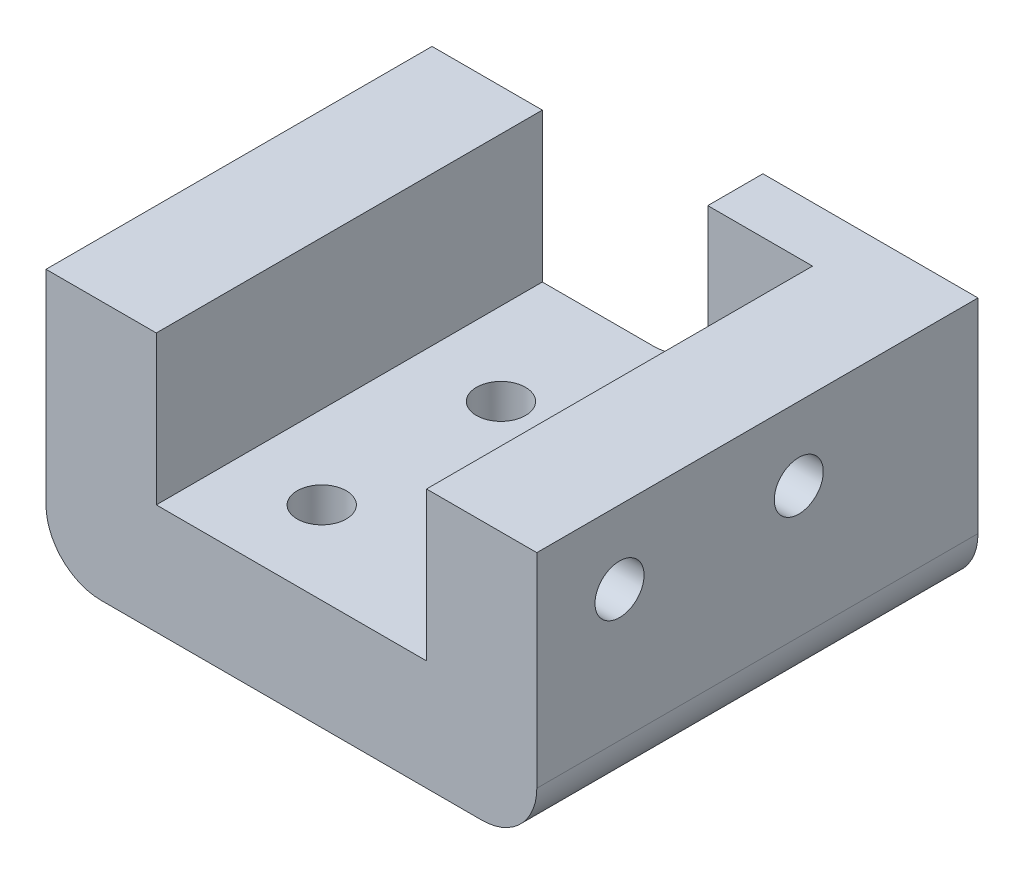
SolidWorks part; units mm, degrees
ref_plane "Front Plane" through (0, 0, 0) normal (0, 0, 1) x (1, 0, 0)
ref_plane "Top Plane" through (0, 0, 0) normal (0, 1, 0) x (1, 0, 0)
ref_plane "Right Plane" through (0, 0, 0) normal (1, 0, 0) x (0, 0, -1)
sketch "Sketch1" plane through (0, 0, 0) normal (0, 1, 0) x (1, 0, 0)
  line L0 (2.075, -3.5) -> (2.825, -3.5)
  line L1 (2.075, -3.5) -> (-2.075, -3.5)
  line L2 (2.075, -3.5) -> (2.075, 3.5) construction
  line L3 (2.075, 3.5) -> (-2.075, 3.5)
  line L4 (-2.075, -3.5) -> (-2.075, 3.5) construction
  line L5 (2.075, -3.5) -> (-2.075, 3.5) construction
  line L6 (2.075, 3.5) -> (-2.075, -3.5) construction
  line L7 (2.825, -3.5) -> (3.825, -3.5)
  line L9 (3.825, 3.5) -> (2.825, 3.5)
  line L10 (2.825, 3.5) -> (2.075, 3.5)
  line L11 (3.825, 3.5) -> (4.825, 3.5)
  line L12 (4.825, 3.5) -> (4.825, -3.5)
  line L13 (4.825, -3.5) -> (3.825, -3.5)
  line L14 (-2.075, 3.5) -> (-4.075, 3.5)
  line L15 (-4.075, 3.5) -> (-4.075, -3.5)
  line L16 (-4.075, -3.5) -> (-2.075, -3.5)
  line L17 (3.825, 3.5) -> (3.825, -3.5) construction
  point P0 (0, 0)
  dimension "D1" = 4.15
  dimension "D2" = 7
  dimension "D3" = 0.75
  dimension "D4" = 1
  dimension "D5" = 1
  dimension "D6" = 2
extrude "Boss-Extrude1" add sketch "Sketch1" along normal blind 2
sketch "Sketch2" plane through (0, 2, 0) normal (0, 1, 0) x (1, 0, 0)
  line L1 (-4.075, 3.5) -> (-2.075, 3.5)
  line L2 (-4.075, 3.5) -> (-4.075, -3.5)
  line L3 (-4.075, -3.5) -> (-2.075, -3.5)
  line L4 (-2.075, 3.5) -> (-2.075, -3.5)
  line L5 (2.825, 3.5) -> (4.825, 3.5)
  line L6 (2.825, 3.5) -> (2.825, -3.5)
  line L7 (2.825, -3.5) -> (4.825, -3.5)
  line L8 (4.825, 3.5) -> (4.825, -3.5)
extrude "Boss-Extrude2" add sketch "Sketch2" along normal blind 2.7
sketch "Sketch3" plane through (2.825, 0, 0) normal (-1, 0, 0) x (0, 0, 1)
  line L13 (-3.5, 4.7) -> (-3.5, 2) construction
  line L14 (-3.5, 2) -> (3.5, 2) construction
  line L15 (-3.5, 4.7) -> (-3.5, 0) construction
  circle A2 centre (-1.25, 3.375) radius 0.4445
  circle A3 centre (2, 3.375) radius 0.4445
  dimension "D4" = 0.889
  dimension "D1" = 1.375
  dimension "D2" = 2.25
  dimension "D3" = 5.5
extrude "Cut-Extrude1" cut sketch "Sketch3" against normal through all
sketch "Sketch5" plane through (0, 0, -3.5) normal (0, 0, -1) x (-1, 0, 0)
  line L0 (-2.075, 0) -> (2.075, 0) construction
  line L1 (-4.825, 4.7) -> (-0.925, 4.7)
  line L2 (-4.825, 4.7) -> (-4.825, 0)
  line L3 (-4.825, 0) -> (-0.925, 0)
  line L4 (-0.925, 4.7) -> (-0.925, 0)
  line L5 (2.075, 4.7) -> (2.075, 2) construction
  dimension "D1" = 3
extrude "Boss-Extrude3" add sketch "Sketch5" along normal blind 1
fillet "Fillet1" radius 1 1 edges at (0.925, 1, -3.5)
sketch "Sketch6" plane through (0, 0, 0) normal (0, -1, 0) x (1, 0, 0)
  line L0 (-2.075, 3.5) -> (-2.075, -3.5) construction
  line L1 (2.075, 3.5) -> (-2.075, 3.5) construction
  circle A0 centre (-0.575, 2) radius 0.4445
  circle A1 centre (-0.575, -1.25) radius 0.4445
  dimension "D2" = 0.889
  dimension "D1" = 1.5
extrude "Cut-Extrude2" cut sketch "Sketch6" against normal through all
fillet "Fillet2" radius 1 2 edges at (4.825, 0, -0.5) (-4.075, 0, 0)
equation "\"Clearance\"=0.75"
equation "\"D3@Sketch1\"=\"Clearance\""
equation "\"NutThickness\"=1"
equation "\"D4@Sketch1\"=\"NutThickness\""
equation "\"LargerWallThickness\"=2"
equation "\"D6@Sketch1\"=\"LargerWallThickness\""
equation "\"D1@Boss-Extrude1\"=\"LargerWallThickness\""
